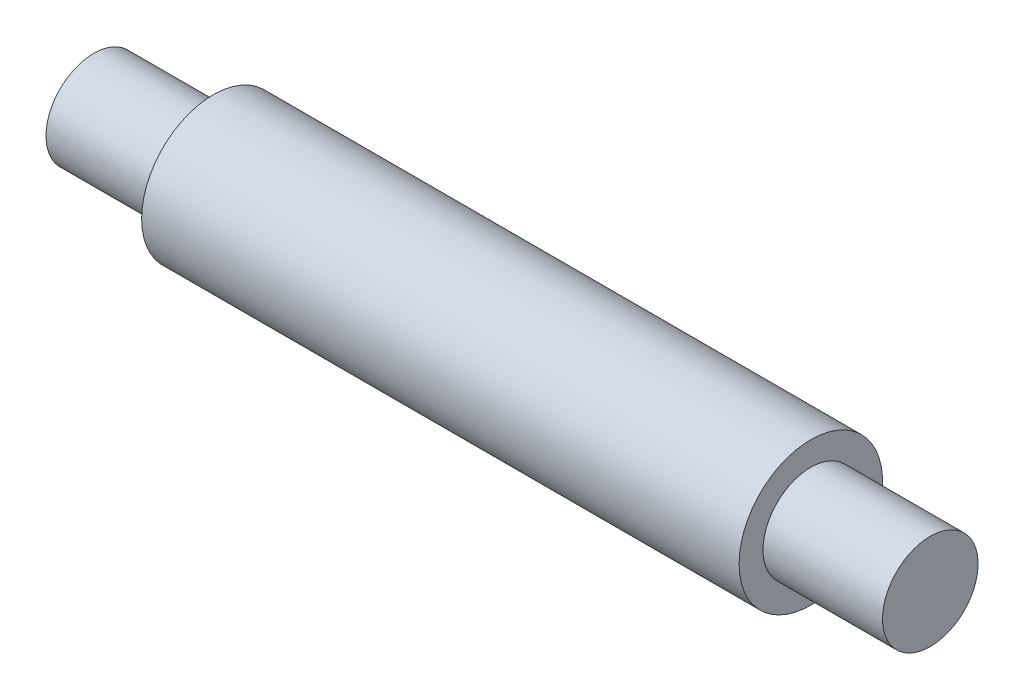
SolidWorks part; units mm, degrees
material "Plain Carbon Steel"
ref_plane "Front Plane" through (0, 0, 0) normal (0, 0, 1) x (1, 0, 0)
ref_plane "Top Plane" through (0, 0, 0) normal (0, 1, 0) x (1, 0, 0)
ref_plane "Right Plane" through (0, 0, 0) normal (1, 0, 0) x (0, 0, -1)
sketch "Sketch1" plane through (0, 0, 0) normal (0, 0, 1) x (1, 0, 0)
  line L0 (0, 0) -> (70, 0)
  line L1 (70, 0) -> (70, 4)
  line L2 (70, 4) -> (60, 4)
  line L3 (60, 4) -> (60, 6)
  line L4 (60, 6) -> (10, 6)
  line L5 (10, 6) -> (10, 4)
  line L6 (10, 4) -> (0, 4)
  line L7 (0, 4) -> (0, 0)
  dimension "D1" = 50
  dimension "D2" = 10
  dimension "D3" = 4
  dimension "D4" = 6
revolve "Revolve1" add sketch "Sketch1" angle 360 about L0
